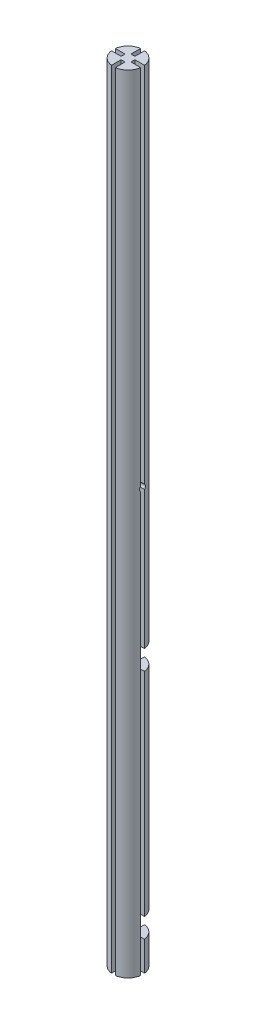
SolidWorks part; units mm, degrees
ref_plane "Front Plane" through (0, 0, 0) normal (0, 0, 1) x (1, 0, 0)
ref_plane "Top Plane" through (0, 0, 0) normal (0, 1, 0) x (1, 0, 0)
ref_plane "Right Plane" through (0, 0, 0) normal (1, 0, 0) x (0, 0, -1)
sketch "Sketch1" plane through (0, 0, 0) normal (0, 1, 0) x (1, 0, 0)
  line L5 (0, 194.8226) -> (0, 75) construction
  line L18 (-10, 74.3303) -> (-10, 25)
  line L19 (-10, 25) -> (10, 25)
  line L20 (10, 74.3303) -> (10, 25)
  line L21 (-29.2048, 0) -> (25.2155, 0) construction
  line L22 (74.3303, -10) -> (25, -10)
  line L23 (74.3303, 10) -> (25, 10)
  line L24 (25, 10) -> (25, -10)
  line L25 (-10, -74.3303) -> (-10, -25)
  line L26 (10, -74.3303) -> (10, -25)
  line L27 (10, -25) -> (-10, -25)
  line L28 (-74.3303, 10) -> (-25, 10)
  line L29 (-74.3303, -10) -> (-25, -10)
  line L30 (-25, -10) -> (-25, 10)
  line L31 (0, 75) -> (0, 25) construction
  line L32 (0, 25) -> (0, -243.8201) construction
  arc A2 (-10, 74.3303) -> (-74.3303, 10) centre (0, 0) ccw
  arc A3 (-74.3303, -10) -> (-10, -74.3303) centre (0, 0) ccw
  arc A4 (10, -74.3303) -> (74.3303, -10) centre (0, 0) ccw
  arc A5 (74.3303, 10) -> (10, 74.3303) centre (0, 0) ccw
  arc A6 (-10, 74.3303) -> (29.2889, 69.0446) centre (0, 0) cw
  point P1 (0, 25)
  point P4 (0, 93.7498)
  point P24 (-100, 0)
  point P29 (0, 0)
  point P30 (0, 0)
  dimension "D1" = 150
  dimension "D2" = 20
  dimension "D3" = 50
  dimension "D4" = 4
extrude "Boss-Extrude2" add sketch "Sketch1" along normal blind 4000 contours A2 L28 L30 L29 A3 L25 L27 L26 A4 L22 L24 L23 A5 L20 L19 L18
sketch "Sketch2" plane through (0, 0, 0) normal (0, 1, 0) x (1, 0, 0)
  line L0 (0, 74.3303) -> (0, 0)
  line L1 (74.3303, 74.3303) -> (74.3303, 0)
  line L2 (74.3303, 74.3303) -> (0, 74.3303)
  line L3 (74.3303, 0) -> (0, 0)
extrude "Cut-Extrude1" cut sketch "Sketch2" along normal mid plane 100 from offset 200
extrude "Cut-Extrude2" cut sketch "Sketch2<2>" against normal mid plane 100 from offset 1380
sketch "Sketch2<2>" plane through (0, 0, 0) normal (0, 1, 0) x (1, 0, 0) same geometry as "Sketch2"
ref_plane "Plane1" through (74.3303, 0, 0) normal (1, 0, 0) x (0, 0, -1)
ref_plane "Plane2" through (0, 0, -74.3303) normal (0, 0, -1) x (-1, 0, 0)
sketch "Sketch3" plane through (74.3303, 0, 0) normal (1, 0, 0) x (0, 0, -1)
  circle A0 centre (0, 2143) radius 15.2
extrude "Cut-Extrude3" cut sketch "Sketch3" against normal up to surface (49.3303 mm away) up to face at (25, 1193.3333, -3.3333)
sketch "Sketch4" plane through (0, 0, -74.3303) normal (0, 0, -1) x (-1, 0, 0)
  circle A2 centre (0, 2143) radius 15.2
extrude "Cut-Extrude4" cut sketch "Sketch4" against normal up to surface (49.3303 mm away) up to face at (3.3333, 1193.3333, -25)
